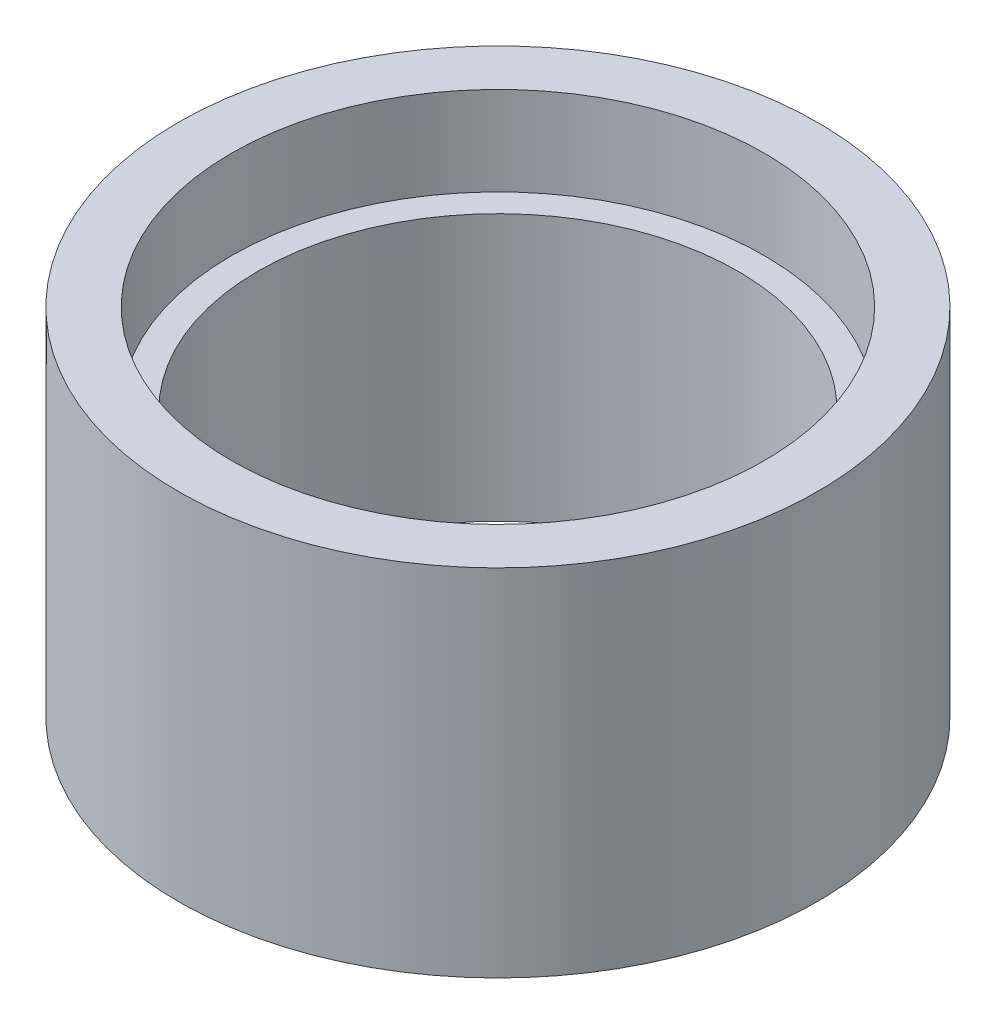
SolidWorks part; units mm, degrees
material "POM Acetal Copolymer"
ref_plane "Front" through (0, 0, 0) normal (0, 0, 1) x (1, 0, 0)
ref_plane "Top" through (0, 0, 0) normal (0, 1, 0) x (1, 0, 0)
ref_plane "Right" through (0, 0, 0) normal (1, 0, 0) x (0, 0, -1)
ref_axis "Center Axis" through (0, 0, 55) along (0, 0, -1)
sketch "Sketch1" plane through (0, 0, 0) normal (0, 0, 1) x (1, 0, 0)
  line L1 (0, 0) -> (12, 0)
  line L2 (0, 0) -> (0, -13.3321)
  line L3 (0, -13.3321) -> (12, -13.3321)
  line L4 (12, 0) -> (12, -13.3321)
  line L5 (0, 0) -> (10, 0)
  line L6 (0, 0) -> (0, -3.3321)
  line L7 (0, -3.3321) -> (10, -3.3321)
  line L8 (10, 0) -> (10, -3.3321)
  line L9 (12, -13.3321) -> (9, -13.3321)
  line L10 (12, -13.3321) -> (12, -3.3321)
  line L11 (12, -3.3321) -> (9, -3.3321)
  line L12 (9, -13.3321) -> (9, -3.3321)
  dimension "D1" = 12
  dimension "D2" = 2
  dimension "D3" = 3.3321
  dimension "D4" = 1
  dimension "D5" = 10
revolve "Revolve1" add sketch "Sketch1" angle 360 about L2 region at (11, -1.6661, 0) region at (10.5, -8.3321, 0)
equation "\"WallThickness\" = 2mm"
equation "\"D1@Sketch1\"=\"PiezoDiameter\"/2 +\"WallThickness\""
equation "\"PiezoDiameter\"= 20mm"
equation "\"PiezoThickness\"= 2.8321mm"
equation "\"BackingThickness\"= 10mm"
equation "\"MatchingThickness\"= 0.5mm"
equation "\"ShelfThickness\"= 1mm"
equation "\"D2@Sketch1\"=\"WallThickness\""
equation "\"D3@Sketch1\"=\"PiezoThickness\"+\"MatchingThickness\""
equation "\"D4@Sketch1\"=\"ShelfThickness\""
equation "\"D5@Sketch1\"=\"BackingThickness\""
